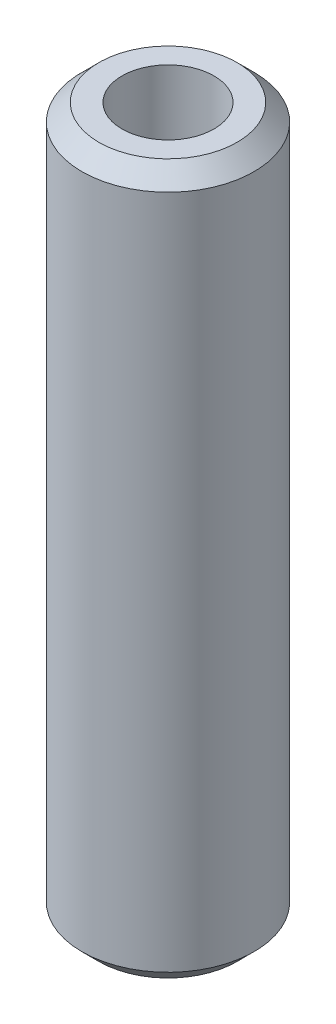
SolidWorks part; units mm, degrees
ref_plane "Front Plane" through (0, 0, 0) normal (0, 0, 1) x (1, 0, 0)
ref_plane "Top Plane" through (0, 0, 0) normal (0, 1, 0) x (1, 0, 0)
ref_plane "Right Plane" through (0, 0, 0) normal (1, 0, 0) x (0, 0, -1)
sketch "Sketch1" plane through (0, 0, 0) normal (0, 1, 0) x (1, 0, 0)
  circle A0 centre (0, 0) radius 5
  dimension "SHAFT_OD" = 10
extrude "Boss-Extrude1" add sketch "Sketch1" along normal blind 41.2162
sketch "Sketch2" plane through (0, 0, 0) normal (0, 1, 0) x (1, 0, 0)
  circle A0 centre (0, 0) radius 2.6736
  dimension "BORE_D" = 5.3471
extrude "Cut-Extrude1" cut sketch "Sketch2" along normal through all
chamfer "Chamfer1" distance 0.9841 angle 45 2 edges at (0, 41.2162, 5) (0, 0, 5)
